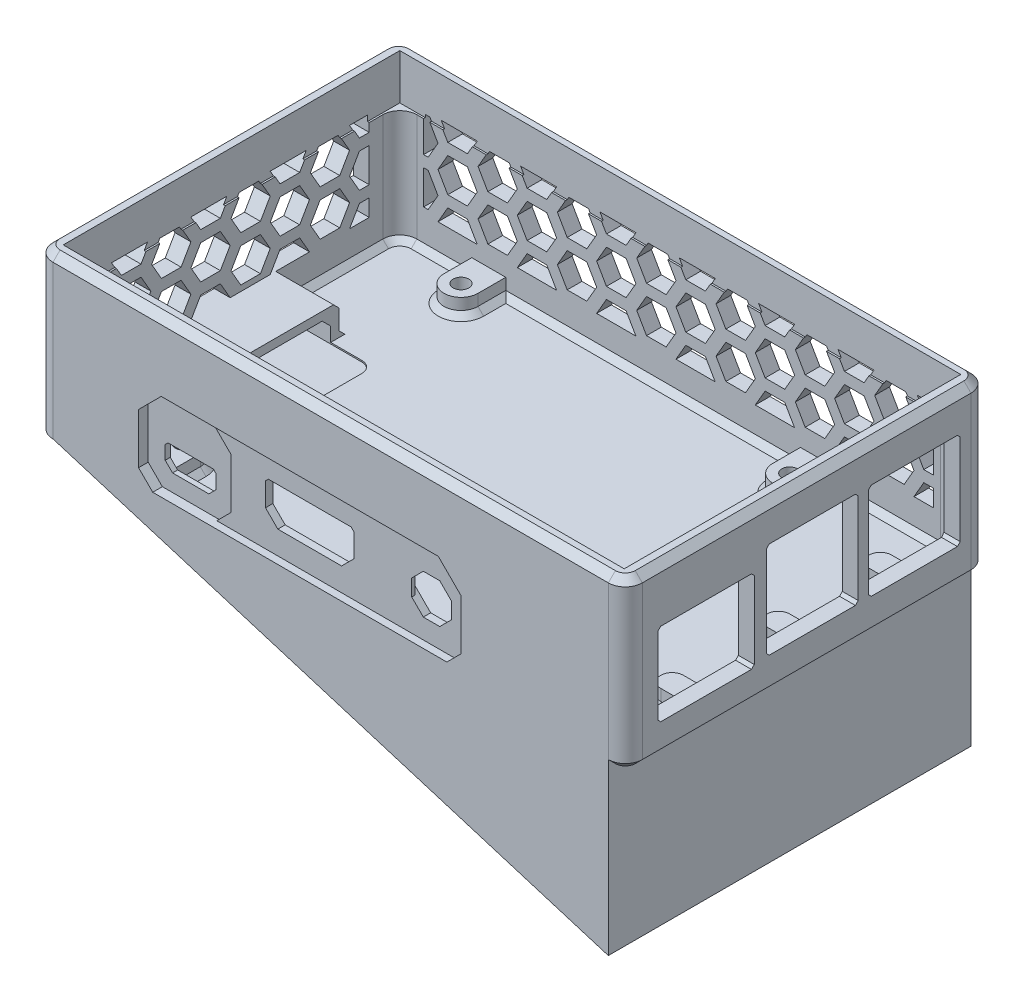
SolidWorks part; units mm, degrees
ref_plane "Front Plane" through (0, 0, 0) normal (0, 0, 1) x (1, 0, 0)
ref_plane "Top Plane" through (0, 0, 0) normal (0, 1, 0) x (1, 0, 0)
ref_plane "Right Plane" through (0, 0, 0) normal (1, 0, 0) x (0, 0, -1)
sketch "Sketch1" plane through (0, 0, 0) normal (0, 1, 0) x (1, 0, 0)
  line L0 (1, 28) -> (0, 28) construction
  line L1 (0, 0) -> (-85, 0) construction
  line L2 (0, 0) -> (0, 56) construction
  line L3 (0, 56) -> (-85, 56) construction
  line L4 (-85, 0) -> (-85, 56) construction
  line L5 (-97, 57.2) -> (1, 57.2) construction
  line L6 (-97, 57.2) -> (-97, -1.2) construction
  line L7 (-97, -1.2) -> (1, -1.2) construction
  line L8 (1, 57.2) -> (1, -1.2) construction
  circle A0 centre (-81.5, 52.5) radius 1.375 construction
  circle A1 centre (-23.5, 52.5) radius 1.375 construction
  circle A2 centre (-81.5, 3.5) radius 1.375 construction
  circle A3 centre (-23.5, 3.5) radius 1.375 construction
  dimension "D3" = 2.75
  dimension "D1" = 56
  dimension "D2" = 85
  dimension "D4" = 49
  dimension "D5" = 58
  dimension "D6" = 3.5
  dimension "D7" = 3.5
  dimension "D8" = 98
  dimension "D9" = 58.4
  dimension "D10" = 15.5
sketch "Sketch2" plane through (0, 0, 0) normal (0, 1, 0) x (1, 0, 0)
  line L0 (-84.5, -2.5) -> (-84.5, 3.5)
  line L2 (-78.5, 3.5) -> (-78.5, -2.5)
  line L3 (-81.5, 3.5) -> (-23.5, 3.5) construction
  line L4 (-81.5, 3.5) -> (-81.5, 52.5) construction
  line L5 (-52.5, 3.5) -> (-52.5, 28) construction
  line L6 (-52.5, 28) -> (-81.5, 28) construction
  line L7 (-84.5, -2.5) -> (-78.5, -2.5)
  line L8 (-20.5, -2.5) -> (-26.5, -2.5)
  line L9 (-26.5, 3.5) -> (-26.5, -2.5)
  line L10 (-20.5, -2.5) -> (-20.5, 3.5)
  line L11 (-20.5, 58.5) -> (-20.5, 52.5)
  line L12 (-26.5, 52.5) -> (-26.5, 58.5)
  line L13 (-20.5, 58.5) -> (-26.5, 58.5)
  line L14 (-84.5, 58.5) -> (-78.5, 58.5)
  line L15 (-78.5, 52.5) -> (-78.5, 58.5)
  line L16 (-84.5, 58.5) -> (-84.5, 52.5)
  arc A0 (-84.5, 3.5) -> (-78.5, 3.5) centre (-81.5, 3.5) cw
  circle A1 centre (-81.5, 3.5) radius 1.375 construction
  circle A2 centre (-81.5, 3.5) radius 1.375
  circle A3 centre (-23.5, 3.5) radius 1.375
  arc A4 (-20.5, 3.5) -> (-26.5, 3.5) centre (-23.5, 3.5) ccw
  arc A5 (-20.5, 52.5) -> (-26.5, 52.5) centre (-23.5, 52.5) cw
  circle A6 centre (-23.5, 52.5) radius 1.375
  circle A7 centre (-81.5, 52.5) radius 1.375
  arc A8 (-84.5, 52.5) -> (-78.5, 52.5) centre (-81.5, 52.5) ccw
  dimension "D1" = 2.75
  dimension "D2" = 6
  dimension "D3" = 6
extrude "Boss-Extrude1" add sketch "Sketch2" along normal blind 4.5
sketch "Sketch4" plane through (0, 0, 0) normal (0, 1, 0) x (1, 0, 0)
  line L0 (0, 28) -> (4, 28) construction
  line L1 (-100, 60) -> (4, 60)
  line L2 (-100, 60) -> (-100, -4)
  line L3 (-100, -4) -> (4, -4)
  line L4 (4, 60) -> (4, -4)
  line L5 (0, 0) -> (0, 56) construction
  line L7 (1, 57.2) -> (1, -1.2) construction
  line L9 (-97, 57.2) -> (-97, -1.2) construction
  dimension "D1" = 64
  dimension "D2" = 3
  dimension "D3" = 3
extrude "Boss-Extrude2" add sketch "Sketch4" along normal blind 1.5
sketch "Sketch5" plane through (0, 0, 0) normal (0, -1, 0) x (1, 0, 0)
  circle A0 centre (-81.5, -3.5) radius 2.6
  circle A1 centre (-23.5, -3.5) radius 2.6
  circle A2 centre (-23.5, -52.5) radius 2.6
  circle A3 centre (-81.5, -52.5) radius 2.6
  dimension "D1" = 5.2
extrude "Cut-Extrude1" cut sketch "Sketch5" against normal offset from surface (2.5 mm away) 2 up to face at (-81.5, 4.5, -1.25)
sketch "Sketch6" plane through (0, 1.5, 0) normal (0, 1, 0) x (1, 0, 0)
  line L0 (-97, 57.2) -> (-97, -1.2) construction
  line L1 (-100, 60) -> (4, 60)
  line L2 (-100, 60) -> (-100, -4)
  line L3 (-100, -4) -> (4, -4)
  line L4 (4, 60) -> (4, -4)
  line L5 (-97.5, 57.7) -> (1.5, 57.7)
  line L6 (-97.5, 57.7) -> (-97.5, -1.7)
  line L7 (-97.5, -1.7) -> (1.5, -1.7)
  line L8 (1.5, 57.7) -> (1.5, -1.7)
  line L9 (-97, 57.2) -> (1, 57.2) construction
  line L10 (1, 57.2) -> (1, -1.2) construction
  line L11 (-97, -1.2) -> (1, -1.2) construction
  dimension "D1" = 0.5
  dimension "D2" = 0.5
  dimension "D3" = 0.5
  dimension "D4" = 0.5
extrude "Boss-Extrude3" add sketch "Sketch6" along normal blind 28
sketch "Sketch10" plane through (0, 1.5, 0) normal (0, 1, 0) x (1, 0, 0)
  line L0 (1.5, 49) -> (-2, 49)
  line L1 (1.5, -1.7) -> (1.5, 57.7) construction
  line L2 (-2, 45) -> (1.5, 45)
  line L3 (1.5, 45) -> (1.5, 49)
  line L4 (1.5, 31) -> (-2, 31)
  line L5 (-2, 27) -> (1.5, 27)
  line L6 (1.5, 27) -> (1.5, 31)
  line L7 (1.5, 12.25) -> (-2, 12.25)
  line L8 (-2, 8.25) -> (1.5, 8.25)
  line L9 (1.5, 8.25) -> (1.5, 12.25)
  line L10 (0, 0) -> (0, 56) construction
  arc A0 (-2, 49) -> (-2, 45) centre (-2, 47) ccw
  arc A1 (-2, 31) -> (-2, 27) centre (-2, 29) ccw
  arc A2 (-2, 12.25) -> (-2, 8.25) centre (-2, 10.25) ccw
  point P19 (-4, 47)
  dimension "D1" = 4
  dimension "D2" = 4
  dimension "D3" = 10.25
  dimension "D4" = 29
  dimension "D5" = 47
extrude "Boss-Extrude4" add sketch "Sketch10" along normal up to surface (3 mm away) up to face at (-23.5, 4.5, -54.35)
sketch "Sketch18" plane through (0, 1.5, 0) normal (0, 1, 0) x (1, 0, 0)
  line L0 (-97.2, 57.4) -> (1.2, 57.4)
  line L1 (-97.5, 57.7) -> (1.5, 57.7)
  line L2 (-97.5, 57.7) -> (-97.5, -1.7)
  line L3 (-97.5, -1.7) -> (1.5, -1.7)
  line L4 (1.5, 57.7) -> (1.5, -1.7)
  line L5 (1.2, 57.4) -> (1.2, -1.4)
  line L6 (-97.2, -1.4) -> (1.2, -1.4)
  line L7 (-97.2, 57.4) -> (-97.2, -1.4)
  dimension "D1" = 0.3
extrude "Boss-Extrude6" add sketch "Sketch18" along normal blind 20
sketch "Sketch19" plane through (0, 0, -60) normal (0, 0, -1) x (-1, 0, 0)
  line L4 (5.5981, 8.5) -> (7.3301, 9.5) construction
  line L5 (6.4641, 7) -> (4.7321, 10)
  line L6 (4.7321, 10) -> (1.2679, 10)
  line L7 (1.2679, 10) -> (-0.4641, 7)
  line L8 (3, 7) -> (93, 7)
  line L9 (93, 7) -> (93, 22.5)
  line L10 (93, 22.5) -> (3, 22.5)
  line L11 (3, 22.5) -> (3, 7)
  line L12 (3, 7) -> (93, 7)
  line L13 (93, 7) -> (93, 22.5)
  line L14 (93, 22.5) -> (3, 22.5)
  line L15 (3, 22.5) -> (3, 7)
  line L16 (-0.4641, 7) -> (1.2679, 4)
  line L17 (1.2679, 4) -> (4.7321, 4)
  line L18 (4.7321, 4) -> (6.4641, 7)
  line L19 (11.6603, 14) -> (8.1962, 14)
  line L20 (8.1962, 14) -> (6.4641, 11)
  line L21 (6.4641, 11) -> (8.1962, 8)
  line L22 (8.1962, 8) -> (11.6603, 8)
  line L23 (11.6603, 8) -> (13.3923, 11)
  line L24 (13.3923, 11) -> (11.6603, 14)
  line L25 (20.4641, 7) -> (18.7321, 10)
  line L26 (18.7321, 10) -> (15.2679, 10)
  line L27 (15.2679, 10) -> (13.5359, 7)
  line L28 (13.5359, 7) -> (15.2679, 4)
  line L29 (15.2679, 4) -> (18.7321, 4)
  line L30 (18.7321, 4) -> (20.4641, 7)
  line L31 (25.6603, 14) -> (22.1962, 14)
  line L32 (22.1962, 14) -> (20.4641, 11)
  line L33 (20.4641, 11) -> (22.1962, 8)
  line L34 (22.1962, 8) -> (25.6603, 8)
  line L35 (25.6603, 8) -> (27.3923, 11)
  line L36 (27.3923, 11) -> (25.6603, 14)
  line L37 (19.5981, 8.5) -> (21.3301, 9.5) construction
  line L38 (34.4641, 7) -> (32.7321, 10)
  line L39 (32.7321, 10) -> (29.2679, 10)
  line L40 (29.2679, 10) -> (27.5359, 7)
  line L41 (27.5359, 7) -> (29.2679, 4)
  line L42 (29.2679, 4) -> (32.7321, 4)
  line L43 (32.7321, 4) -> (34.4641, 7)
  line L44 (39.6603, 14) -> (36.1962, 14)
  line L45 (36.1962, 14) -> (34.4641, 11)
  line L46 (34.4641, 11) -> (36.1962, 8)
  line L47 (36.1962, 8) -> (39.6603, 8)
  line L48 (39.6603, 8) -> (41.3923, 11)
  line L49 (41.3923, 11) -> (39.6603, 14)
  line L50 (33.5981, 8.5) -> (35.3301, 9.5) construction
  line L51 (48.4641, 7) -> (46.7321, 10)
  line L52 (46.7321, 10) -> (43.2679, 10)
  line L53 (43.2679, 10) -> (41.5359, 7)
  line L54 (41.5359, 7) -> (43.2679, 4)
  line L55 (43.2679, 4) -> (46.7321, 4)
  line L56 (46.7321, 4) -> (48.4641, 7)
  line L57 (53.6603, 14) -> (50.1962, 14)
  line L58 (50.1962, 14) -> (48.4641, 11)
  line L59 (48.4641, 11) -> (50.1962, 8)
  line L60 (50.1962, 8) -> (53.6603, 8)
  line L61 (53.6603, 8) -> (55.3923, 11)
  line L62 (55.3923, 11) -> (53.6603, 14)
  line L63 (47.5981, 8.5) -> (49.3301, 9.5) construction
  line L64 (62.4641, 7) -> (60.7321, 10)
  line L65 (60.7321, 10) -> (57.2679, 10)
  line L66 (57.2679, 10) -> (55.5359, 7)
  line L67 (55.5359, 7) -> (57.2679, 4)
  line L68 (57.2679, 4) -> (60.7321, 4)
  line L69 (60.7321, 4) -> (62.4641, 7)
  line L70 (67.6603, 14) -> (64.1962, 14)
  line L71 (64.1962, 14) -> (62.4641, 11)
  line L72 (62.4641, 11) -> (64.1962, 8)
  line L73 (64.1962, 8) -> (67.6603, 8)
  line L74 (67.6603, 8) -> (69.3923, 11)
  line L75 (69.3923, 11) -> (67.6603, 14)
  line L76 (61.5981, 8.5) -> (63.3301, 9.5) construction
  line L77 (76.4641, 7) -> (74.7321, 10)
  line L78 (74.7321, 10) -> (71.2679, 10)
  line L79 (71.2679, 10) -> (69.5359, 7)
  line L80 (69.5359, 7) -> (71.2679, 4)
  line L81 (71.2679, 4) -> (74.7321, 4)
  line L82 (74.7321, 4) -> (76.4641, 7)
  line L83 (81.6603, 14) -> (78.1962, 14)
  line L84 (78.1962, 14) -> (76.4641, 11)
  line L85 (76.4641, 11) -> (78.1962, 8)
  line L86 (78.1962, 8) -> (81.6603, 8)
  line L87 (81.6603, 8) -> (83.3923, 11)
  line L88 (83.3923, 11) -> (81.6603, 14)
  line L89 (75.5981, 8.5) -> (77.3301, 9.5) construction
  line L90 (90.4641, 7) -> (88.7321, 10)
  line L91 (88.7321, 10) -> (85.2679, 10)
  line L92 (85.2679, 10) -> (83.5359, 7)
  line L93 (83.5359, 7) -> (85.2679, 4)
  line L94 (85.2679, 4) -> (88.7321, 4)
  line L95 (88.7321, 4) -> (90.4641, 7)
  line L96 (95.6603, 14) -> (92.1962, 14)
  line L97 (92.1962, 14) -> (90.4641, 11)
  line L98 (90.4641, 11) -> (92.1962, 8)
  line L99 (92.1962, 8) -> (95.6603, 8)
  line L100 (95.6603, 8) -> (97.3923, 11)
  line L101 (97.3923, 11) -> (95.6603, 14)
  line L102 (89.5981, 8.5) -> (91.3301, 9.5) construction
  line L103 (20.4641, 15) -> (18.7321, 18)
  line L104 (18.7321, 18) -> (15.2679, 18)
  line L105 (15.2679, 18) -> (13.5359, 15)
  line L106 (13.5359, 15) -> (15.2679, 12)
  line L107 (15.2679, 12) -> (18.7321, 12)
  line L108 (18.7321, 12) -> (20.4641, 15)
  line L109 (25.6603, 22) -> (22.1962, 22)
  line L110 (22.1962, 22) -> (20.4641, 19)
  line L111 (20.4641, 19) -> (22.1962, 16)
  line L112 (22.1962, 16) -> (25.6603, 16)
  line L113 (25.6603, 16) -> (27.3923, 19)
  line L114 (27.3923, 19) -> (25.6603, 22)
  line L115 (19.5981, 16.5) -> (21.3301, 17.5) construction
  line L116 (34.4641, 15) -> (32.7321, 18)
  line L117 (32.7321, 18) -> (29.2679, 18)
  line L118 (29.2679, 18) -> (27.5359, 15)
  line L119 (27.5359, 15) -> (29.2679, 12)
  line L120 (29.2679, 12) -> (32.7321, 12)
  line L121 (32.7321, 12) -> (34.4641, 15)
  line L122 (39.6603, 22) -> (36.1962, 22)
  line L123 (36.1962, 22) -> (34.4641, 19)
  line L124 (34.4641, 19) -> (36.1962, 16)
  line L125 (36.1962, 16) -> (39.6603, 16)
  line L126 (39.6603, 16) -> (41.3923, 19)
  line L127 (41.3923, 19) -> (39.6603, 22)
  line L128 (33.5981, 16.5) -> (35.3301, 17.5) construction
  line L129 (48.4641, 15) -> (46.7321, 18)
  line L130 (46.7321, 18) -> (43.2679, 18)
  line L131 (43.2679, 18) -> (41.5359, 15)
  line L132 (41.5359, 15) -> (43.2679, 12)
  line L133 (43.2679, 12) -> (46.7321, 12)
  line L134 (46.7321, 12) -> (48.4641, 15)
  line L135 (53.6603, 22) -> (50.1962, 22)
  line L136 (50.1962, 22) -> (48.4641, 19)
  line L137 (48.4641, 19) -> (50.1962, 16)
  line L138 (50.1962, 16) -> (53.6603, 16)
  line L139 (53.6603, 16) -> (55.3923, 19)
  line L140 (55.3923, 19) -> (53.6603, 22)
  line L141 (47.5981, 16.5) -> (49.3301, 17.5) construction
  line L142 (62.4641, 15) -> (60.7321, 18)
  line L143 (60.7321, 18) -> (57.2679, 18)
  line L144 (57.2679, 18) -> (55.5359, 15)
  line L145 (55.5359, 15) -> (57.2679, 12)
  line L146 (57.2679, 12) -> (60.7321, 12)
  line L147 (60.7321, 12) -> (62.4641, 15)
  line L148 (67.6603, 22) -> (64.1962, 22)
  line L149 (64.1962, 22) -> (62.4641, 19)
  line L150 (62.4641, 19) -> (64.1962, 16)
  line L151 (64.1962, 16) -> (67.6603, 16)
  line L152 (67.6603, 16) -> (69.3923, 19)
  line L153 (69.3923, 19) -> (67.6603, 22)
  line L154 (61.5981, 16.5) -> (63.3301, 17.5) construction
  line L155 (76.4641, 15) -> (74.7321, 18)
  line L156 (74.7321, 18) -> (71.2679, 18)
  line L157 (71.2679, 18) -> (69.5359, 15)
  line L158 (69.5359, 15) -> (71.2679, 12)
  line L159 (71.2679, 12) -> (74.7321, 12)
  line L160 (74.7321, 12) -> (76.4641, 15)
  line L161 (81.6603, 22) -> (78.1962, 22)
  line L162 (78.1962, 22) -> (76.4641, 19)
  line L163 (76.4641, 19) -> (78.1962, 16)
  line L164 (78.1962, 16) -> (81.6603, 16)
  line L165 (81.6603, 16) -> (83.3923, 19)
  line L166 (83.3923, 19) -> (81.6603, 22)
  line L167 (75.5981, 16.5) -> (77.3301, 17.5) construction
  line L168 (90.4641, 15) -> (88.7321, 18)
  line L169 (88.7321, 18) -> (85.2679, 18)
  line L170 (85.2679, 18) -> (83.5359, 15)
  line L171 (83.5359, 15) -> (85.2679, 12)
  line L172 (85.2679, 12) -> (88.7321, 12)
  line L173 (88.7321, 12) -> (90.4641, 15)
  line L174 (95.6603, 22) -> (92.1962, 22)
  line L175 (92.1962, 22) -> (90.4641, 19)
  line L176 (90.4641, 19) -> (92.1962, 16)
  line L177 (92.1962, 16) -> (95.6603, 16)
  line L178 (95.6603, 16) -> (97.3923, 19)
  line L179 (97.3923, 19) -> (95.6603, 22)
  line L180 (89.5981, 16.5) -> (91.3301, 17.5) construction
  line L181 (20.4641, 23) -> (18.7321, 26)
  line L182 (18.7321, 26) -> (15.2679, 26)
  line L183 (15.2679, 26) -> (13.5359, 23)
  line L184 (13.5359, 23) -> (15.2679, 20)
  line L185 (15.2679, 20) -> (18.7321, 20)
  line L186 (18.7321, 20) -> (20.4641, 23)
  line L187 (25.6603, 30) -> (22.1962, 30)
  line L188 (22.1962, 30) -> (20.4641, 27)
  line L189 (20.4641, 27) -> (22.1962, 24)
  line L190 (22.1962, 24) -> (25.6603, 24)
  line L191 (25.6603, 24) -> (27.3923, 27)
  line L192 (27.3923, 27) -> (25.6603, 30)
  line L193 (19.5981, 24.5) -> (21.3301, 25.5) construction
  line L194 (34.4641, 23) -> (32.7321, 26)
  line L195 (32.7321, 26) -> (29.2679, 26)
  line L196 (29.2679, 26) -> (27.5359, 23)
  line L197 (27.5359, 23) -> (29.2679, 20)
  line L198 (29.2679, 20) -> (32.7321, 20)
  line L199 (32.7321, 20) -> (34.4641, 23)
  line L200 (39.6603, 30) -> (36.1962, 30)
  line L201 (36.1962, 30) -> (34.4641, 27)
  line L202 (34.4641, 27) -> (36.1962, 24)
  line L203 (36.1962, 24) -> (39.6603, 24)
  line L204 (39.6603, 24) -> (41.3923, 27)
  line L205 (41.3923, 27) -> (39.6603, 30)
  line L206 (33.5981, 24.5) -> (35.3301, 25.5) construction
  line L207 (48.4641, 23) -> (46.7321, 26)
  line L208 (46.7321, 26) -> (43.2679, 26)
  line L209 (43.2679, 26) -> (41.5359, 23)
  line L210 (41.5359, 23) -> (43.2679, 20)
  line L211 (43.2679, 20) -> (46.7321, 20)
  line L212 (46.7321, 20) -> (48.4641, 23)
  line L213 (53.6603, 30) -> (50.1962, 30)
  line L214 (50.1962, 30) -> (48.4641, 27)
  line L215 (48.4641, 27) -> (50.1962, 24)
  line L216 (50.1962, 24) -> (53.6603, 24)
  line L217 (53.6603, 24) -> (55.3923, 27)
  line L218 (55.3923, 27) -> (53.6603, 30)
  line L219 (47.5981, 24.5) -> (49.3301, 25.5) construction
  line L220 (62.4641, 23) -> (60.7321, 26)
  line L221 (60.7321, 26) -> (57.2679, 26)
  line L222 (57.2679, 26) -> (55.5359, 23)
  line L223 (55.5359, 23) -> (57.2679, 20)
  line L224 (57.2679, 20) -> (60.7321, 20)
  line L225 (60.7321, 20) -> (62.4641, 23)
  line L226 (67.6603, 30) -> (64.1962, 30)
  line L227 (64.1962, 30) -> (62.4641, 27)
  line L228 (62.4641, 27) -> (64.1962, 24)
  line L229 (64.1962, 24) -> (67.6603, 24)
  line L230 (67.6603, 24) -> (69.3923, 27)
  line L231 (69.3923, 27) -> (67.6603, 30)
  line L232 (61.5981, 24.5) -> (63.3301, 25.5) construction
  line L233 (76.4641, 23) -> (74.7321, 26)
  line L234 (74.7321, 26) -> (71.2679, 26)
  line L235 (71.2679, 26) -> (69.5359, 23)
  line L236 (69.5359, 23) -> (71.2679, 20)
  line L237 (71.2679, 20) -> (74.7321, 20)
  line L238 (74.7321, 20) -> (76.4641, 23)
  line L239 (81.6603, 30) -> (78.1962, 30)
  line L240 (78.1962, 30) -> (76.4641, 27)
  line L241 (76.4641, 27) -> (78.1962, 24)
  line L242 (78.1962, 24) -> (81.6603, 24)
  line L243 (81.6603, 24) -> (83.3923, 27)
  line L244 (83.3923, 27) -> (81.6603, 30)
  line L245 (75.5981, 24.5) -> (77.3301, 25.5) construction
  line L246 (90.4641, 23) -> (88.7321, 26)
  line L247 (88.7321, 26) -> (85.2679, 26)
  line L248 (85.2679, 26) -> (83.5359, 23)
  line L249 (83.5359, 23) -> (85.2679, 20)
  line L250 (85.2679, 20) -> (88.7321, 20)
  line L251 (88.7321, 20) -> (90.4641, 23)
  line L252 (95.6603, 30) -> (92.1962, 30)
  line L253 (92.1962, 30) -> (90.4641, 27)
  line L254 (90.4641, 27) -> (92.1962, 24)
  line L255 (92.1962, 24) -> (95.6603, 24)
  line L256 (95.6603, 24) -> (97.3923, 27)
  line L257 (97.3923, 27) -> (95.6603, 30)
  line L258 (89.5981, 24.5) -> (91.3301, 25.5) construction
  line L259 (6.4641, 15) -> (4.7321, 18)
  line L260 (4.7321, 18) -> (1.2679, 18)
  line L261 (1.2679, 18) -> (-0.4641, 15)
  line L262 (-0.4641, 15) -> (1.2679, 12)
  line L263 (1.2679, 12) -> (4.7321, 12)
  line L264 (4.7321, 12) -> (6.4641, 15)
  line L265 (11.6603, 22) -> (8.1962, 22)
  line L266 (8.1962, 22) -> (6.4641, 19)
  line L267 (6.4641, 19) -> (8.1962, 16)
  line L268 (8.1962, 16) -> (11.6603, 16)
  line L269 (11.6603, 16) -> (13.3923, 19)
  line L270 (13.3923, 19) -> (11.6603, 22)
  line L271 (5.5981, 16.5) -> (7.3301, 17.5) construction
  line L272 (6.4641, 23) -> (4.7321, 26)
  line L273 (4.7321, 26) -> (1.2679, 26)
  line L274 (1.2679, 26) -> (-0.4641, 23)
  line L275 (-0.4641, 23) -> (1.2679, 20)
  line L276 (1.2679, 20) -> (4.7321, 20)
  line L277 (4.7321, 20) -> (6.4641, 23)
  line L278 (11.6603, 30) -> (8.1962, 30)
  line L279 (8.1962, 30) -> (6.4641, 27)
  line L280 (6.4641, 27) -> (8.1962, 24)
  line L281 (8.1962, 24) -> (11.6603, 24)
  line L282 (11.6603, 24) -> (13.3923, 27)
  line L283 (13.3923, 27) -> (11.6603, 30)
  line L284 (5.5981, 24.5) -> (7.3301, 25.5) construction
  circle A0 centre (3, 7) radius 3 construction
  circle A1 centre (9.9282, 11) radius 3 construction
  circle A2 centre (17, 7) radius 3 construction
  circle A3 centre (23.9282, 11) radius 3 construction
  circle A4 centre (31, 7) radius 3 construction
  circle A5 centre (37.9282, 11) radius 3 construction
  circle A6 centre (45, 7) radius 3 construction
  circle A7 centre (51.9282, 11) radius 3 construction
  circle A8 centre (59, 7) radius 3 construction
  circle A9 centre (65.9282, 11) radius 3 construction
  circle A10 centre (73, 7) radius 3 construction
  circle A11 centre (79.9282, 11) radius 3 construction
  circle A12 centre (87, 7) radius 3 construction
  circle A13 centre (93.9282, 11) radius 3 construction
  circle A14 centre (17, 15) radius 3 construction
  circle A15 centre (23.9282, 19) radius 3 construction
  circle A16 centre (31, 15) radius 3 construction
  circle A17 centre (37.9282, 19) radius 3 construction
  circle A18 centre (45, 15) radius 3 construction
  circle A19 centre (51.9282, 19) radius 3 construction
  circle A20 centre (59, 15) radius 3 construction
  circle A21 centre (65.9282, 19) radius 3 construction
  circle A22 centre (73, 15) radius 3 construction
  circle A23 centre (79.9282, 19) radius 3 construction
  circle A24 centre (87, 15) radius 3 construction
  circle A25 centre (93.9282, 19) radius 3 construction
  circle A26 centre (17, 23) radius 3 construction
  circle A27 centre (23.9282, 27) radius 3 construction
  circle A28 centre (31, 23) radius 3 construction
  circle A29 centre (37.9282, 27) radius 3 construction
  circle A30 centre (45, 23) radius 3 construction
  circle A31 centre (51.9282, 27) radius 3 construction
  circle A32 centre (59, 23) radius 3 construction
  circle A33 centre (65.9282, 27) radius 3 construction
  circle A34 centre (73, 23) radius 3 construction
  circle A35 centre (79.9282, 27) radius 3 construction
  circle A36 centre (87, 23) radius 3 construction
  circle A37 centre (93.9282, 27) radius 3 construction
  circle A38 centre (3, 15) radius 3 construction
  circle A39 centre (9.9282, 19) radius 3 construction
  circle A40 centre (3, 23) radius 3 construction
  circle A41 centre (9.9282, 27) radius 3 construction
  dimension "D2" = 6
  dimension "D3" = 2
  dimension "D1" = 7
  dimension "D4" = 7
  dimension "D5" = 3
extrude "Cut-Extrude8" cut sketch "Sketch19" against normal up to next (2.6 mm away) contours L6 L15 L12 L5 | L263 L264 L259 L260 L15 | L276 L277 L14 L15 | L185 L186 L14 L184 | L269 L270 L265 L266 L267 L268 | L23 L24 L19 L20 L21 L22 | L107 L108 L103 L104 L105 L106 | L26 L27 L12 L25 | L35 L36 L31 L32 L33 L34 | L39 L40 L12 L38 | L48 L49 L44 L45 L46 L47 | L52 L53 L12 L51 | L61 L62 L57 L58 L59 L60 | L65 L66 L12 L64 | L74 L75 L70 L71 L72 L73 | L78 L79 L12 L77 | L87 L88 L83 L84 L85 L86 | L91 L92 L12 L90 | L98 L99 L13 L96 L97 | L176 L177 L13 L174 L175 | L250 L251 L14 L249 | L172 L173 L168 L169 L170 L171 | L165 L166 L161 L162 L163 L164 | L237 L238 L14 L236 | L159 L160 L155 L156 L157 L158 | L152 L153 L148 L149 L150 L151 | L224 L225 L14 L223 | L146 L147 L142 L143 L144 L145 | L139 L140 L135 L136 L137 L138 | L211 L212 L14 L210 | L198 L199 L14 L197 | L113 L114 L109 L110 L111 L112 | L120 L121 L116 L117 L118 L119 | L126 L127 L122 L123 L124 L125 | L133 L134 L129 L130 L131 L132 region at (-4.3472, 8.3333, -60) region at (-17, 8.3333, -60) region at (-4.3472, 15, -60) region at (-31, 8.3333, -60) region at (-4.2622, 21.3725, -60) region at (-45, 8.3333, -60) region at (-59, 8.3333, -60) region at (-17, 21.3725, -60) region at (-73, 8.3333, -60) region at (-31, 21.3725, -60) region at (-87, 8.3333, -60) region at (-45, 21.3725, -60) region at (-59, 21.3725, -60) region at (-92.0902, 11, -60) region at (-73, 21.3725, -60) region at (-92.0902, 19, -60) region at (-87, 21.3725, -60) region at (-9.9282, 11, -60) region at (-23.9282, 11, -60) region at (-37.9282, 11, -60) region at (-51.9282, 11, -60) region at (-65.9282, 11, -60) region at (-79.9282, 11, -60) region at (-17, 15, -60) region at (-23.9282, 19, -60) region at (-31, 15, -60) region at (-37.9282, 19, -60) region at (-45, 15, -60) region at (-51.9282, 19, -60) region at (-59, 15, -60) region at (-65.9282, 19, -60) region at (-73, 15, -60) region at (-79.9282, 19, -60) region at (-87, 15, -60) region at (-9.9282, 19, -60)
sketch "Sketch21" plane through (-100, 0, 0) normal (-1, 0, 0) x (0, 0, 1)
  line L0 (-60, 29.5) -> (4, 29.5) construction
  line L1 (-52, 22.5) -> (-4, 22.5)
  line L2 (-52, 22.5) -> (-52, 7)
  line L3 (-52, 7) -> (-4, 7)
  line L4 (-4, 22.5) -> (-4, 7)
  line L5 (-60, 0) -> (4, 0) construction
  line L6 (-60, 29.5) -> (-60, 0) construction
  line L7 (4, 29.5) -> (4, 0) construction
  line L8 (-52, 7) -> (-45.0718, 11) construction
  line L9 (-53.7321, 10) -> (-55.4641, 7)
  line L10 (-55.4641, 7) -> (-53.7321, 4)
  line L11 (-53.7321, 4) -> (-50.2679, 4)
  line L12 (-50.2679, 4) -> (-48.5359, 7)
  line L13 (-48.5359, 7) -> (-50.2679, 10)
  line L14 (-50.2679, 10) -> (-53.7321, 10)
  line L15 (-43.3397, 14) -> (-46.8038, 14)
  line L16 (-46.8038, 14) -> (-48.5359, 11)
  line L17 (-48.5359, 11) -> (-46.8038, 8)
  line L18 (-46.8038, 8) -> (-43.3397, 8)
  line L19 (-43.3397, 8) -> (-41.6077, 11)
  line L20 (-41.6077, 11) -> (-43.3397, 14)
  line L21 (-39.7321, 10) -> (-41.4641, 7)
  line L22 (-41.4641, 7) -> (-39.7321, 4)
  line L23 (-39.7321, 4) -> (-36.2679, 4)
  line L24 (-36.2679, 4) -> (-34.5359, 7)
  line L25 (-34.5359, 7) -> (-36.2679, 10)
  line L26 (-36.2679, 10) -> (-39.7321, 10)
  line L27 (-29.3397, 14) -> (-32.8038, 14)
  line L28 (-32.8038, 14) -> (-34.5359, 11)
  line L29 (-34.5359, 11) -> (-32.8038, 8)
  line L30 (-32.8038, 8) -> (-29.3397, 8)
  line L31 (-29.3397, 8) -> (-27.6077, 11)
  line L32 (-27.6077, 11) -> (-29.3397, 14)
  line L33 (-38, 7) -> (-31.0718, 11) construction
  line L34 (-25.7321, 10) -> (-27.4641, 7)
  line L35 (-27.4641, 7) -> (-25.7321, 4)
  line L36 (-25.7321, 4) -> (-22.2679, 4)
  line L37 (-22.2679, 4) -> (-20.5359, 7)
  line L38 (-20.5359, 7) -> (-22.2679, 10)
  line L39 (-22.2679, 10) -> (-25.7321, 10)
  line L40 (-15.3397, 14) -> (-18.8038, 14)
  line L41 (-18.8038, 14) -> (-20.5359, 11)
  line L42 (-20.5359, 11) -> (-18.8038, 8)
  line L43 (-18.8038, 8) -> (-15.3397, 8)
  line L44 (-15.3397, 8) -> (-13.6077, 11)
  line L45 (-13.6077, 11) -> (-15.3397, 14)
  line L46 (-24, 7) -> (-17.0718, 11) construction
  line L47 (-11.7321, 10) -> (-13.4641, 7)
  line L48 (-13.4641, 7) -> (-11.7321, 4)
  line L49 (-11.7321, 4) -> (-8.2679, 4)
  line L50 (-8.2679, 4) -> (-6.5359, 7)
  line L51 (-6.5359, 7) -> (-8.2679, 10)
  line L52 (-8.2679, 10) -> (-11.7321, 10)
  line L53 (-1.3397, 14) -> (-4.8038, 14)
  line L54 (-4.8038, 14) -> (-6.5359, 11)
  line L55 (-6.5359, 11) -> (-4.8038, 8)
  line L56 (-4.8038, 8) -> (-1.3397, 8)
  line L57 (-1.3397, 8) -> (0.3923, 11)
  line L58 (0.3923, 11) -> (-1.3397, 14)
  line L59 (-10, 7) -> (-3.0718, 11) construction
  line L60 (-39.7321, 18) -> (-41.4641, 15)
  line L61 (-41.4641, 15) -> (-39.7321, 12)
  line L62 (-39.7321, 12) -> (-36.2679, 12)
  line L63 (-36.2679, 12) -> (-34.5359, 15)
  line L64 (-34.5359, 15) -> (-36.2679, 18)
  line L65 (-36.2679, 18) -> (-39.7321, 18)
  line L66 (-29.3397, 22) -> (-32.8038, 22)
  line L67 (-32.8038, 22) -> (-34.5359, 19)
  line L68 (-34.5359, 19) -> (-32.8038, 16)
  line L69 (-32.8038, 16) -> (-29.3397, 16)
  line L70 (-29.3397, 16) -> (-27.6077, 19)
  line L71 (-27.6077, 19) -> (-29.3397, 22)
  line L72 (-38, 15) -> (-31.0718, 19) construction
  line L73 (-25.7321, 18) -> (-27.4641, 15)
  line L74 (-27.4641, 15) -> (-25.7321, 12)
  line L75 (-25.7321, 12) -> (-22.2679, 12)
  line L76 (-22.2679, 12) -> (-20.5359, 15)
  line L77 (-20.5359, 15) -> (-22.2679, 18)
  line L78 (-22.2679, 18) -> (-25.7321, 18)
  line L79 (-15.3397, 22) -> (-18.8038, 22)
  line L80 (-18.8038, 22) -> (-20.5359, 19)
  line L81 (-20.5359, 19) -> (-18.8038, 16)
  line L82 (-18.8038, 16) -> (-15.3397, 16)
  line L83 (-15.3397, 16) -> (-13.6077, 19)
  line L84 (-13.6077, 19) -> (-15.3397, 22)
  line L85 (-24, 15) -> (-17.0718, 19) construction
  line L86 (-11.7321, 18) -> (-13.4641, 15)
  line L87 (-13.4641, 15) -> (-11.7321, 12)
  line L88 (-11.7321, 12) -> (-8.2679, 12)
  line L89 (-8.2679, 12) -> (-6.5359, 15)
  line L90 (-6.5359, 15) -> (-8.2679, 18)
  line L91 (-8.2679, 18) -> (-11.7321, 18)
  line L92 (-1.3397, 22) -> (-4.8038, 22)
  line L93 (-4.8038, 22) -> (-6.5359, 19)
  line L94 (-6.5359, 19) -> (-4.8038, 16)
  line L95 (-4.8038, 16) -> (-1.3397, 16)
  line L96 (-1.3397, 16) -> (0.3923, 19)
  line L97 (0.3923, 19) -> (-1.3397, 22)
  line L98 (-10, 15) -> (-3.0718, 19) construction
  line L99 (-39.7321, 26) -> (-41.4641, 23)
  line L100 (-41.4641, 23) -> (-39.7321, 20)
  line L101 (-39.7321, 20) -> (-36.2679, 20)
  line L102 (-36.2679, 20) -> (-34.5359, 23)
  line L103 (-34.5359, 23) -> (-36.2679, 26)
  line L104 (-36.2679, 26) -> (-39.7321, 26)
  line L105 (-29.3397, 30) -> (-32.8038, 30)
  line L106 (-32.8038, 30) -> (-34.5359, 27)
  line L107 (-34.5359, 27) -> (-32.8038, 24)
  line L108 (-32.8038, 24) -> (-29.3397, 24)
  line L109 (-29.3397, 24) -> (-27.6077, 27)
  line L110 (-27.6077, 27) -> (-29.3397, 30)
  line L111 (-38, 23) -> (-31.0718, 27) construction
  line L112 (-25.7321, 26) -> (-27.4641, 23)
  line L113 (-27.4641, 23) -> (-25.7321, 20)
  line L114 (-25.7321, 20) -> (-22.2679, 20)
  line L115 (-22.2679, 20) -> (-20.5359, 23)
  line L116 (-20.5359, 23) -> (-22.2679, 26)
  line L117 (-22.2679, 26) -> (-25.7321, 26)
  line L118 (-15.3397, 30) -> (-18.8038, 30)
  line L119 (-18.8038, 30) -> (-20.5359, 27)
  line L120 (-20.5359, 27) -> (-18.8038, 24)
  line L121 (-18.8038, 24) -> (-15.3397, 24)
  line L122 (-15.3397, 24) -> (-13.6077, 27)
  line L123 (-13.6077, 27) -> (-15.3397, 30)
  line L124 (-24, 23) -> (-17.0718, 27) construction
  line L125 (-11.7321, 26) -> (-13.4641, 23)
  line L126 (-13.4641, 23) -> (-11.7321, 20)
  line L127 (-11.7321, 20) -> (-8.2679, 20)
  line L128 (-8.2679, 20) -> (-6.5359, 23)
  line L129 (-6.5359, 23) -> (-8.2679, 26)
  line L130 (-8.2679, 26) -> (-11.7321, 26)
  line L131 (-1.3397, 30) -> (-4.8038, 30)
  line L132 (-4.8038, 30) -> (-6.5359, 27)
  line L133 (-6.5359, 27) -> (-4.8038, 24)
  line L134 (-4.8038, 24) -> (-1.3397, 24)
  line L135 (-1.3397, 24) -> (0.3923, 27)
  line L136 (0.3923, 27) -> (-1.3397, 30)
  line L137 (-10, 23) -> (-3.0718, 27) construction
  line L138 (-53.7321, 18) -> (-55.4641, 15)
  line L139 (-55.4641, 15) -> (-53.7321, 12)
  line L140 (-53.7321, 12) -> (-50.2679, 12)
  line L141 (-50.2679, 12) -> (-48.5359, 15)
  line L142 (-48.5359, 15) -> (-50.2679, 18)
  line L143 (-50.2679, 18) -> (-53.7321, 18)
  line L144 (-43.3397, 22) -> (-46.8038, 22)
  line L145 (-46.8038, 22) -> (-48.5359, 19)
  line L146 (-48.5359, 19) -> (-46.8038, 16)
  line L147 (-46.8038, 16) -> (-43.3397, 16)
  line L148 (-43.3397, 16) -> (-41.6077, 19)
  line L149 (-41.6077, 19) -> (-43.3397, 22)
  line L150 (-52, 15) -> (-45.0718, 19) construction
  line L151 (-53.7321, 26) -> (-55.4641, 23)
  line L152 (-55.4641, 23) -> (-53.7321, 20)
  line L153 (-53.7321, 20) -> (-50.2679, 20)
  line L154 (-50.2679, 20) -> (-48.5359, 23)
  line L155 (-48.5359, 23) -> (-50.2679, 26)
  line L156 (-50.2679, 26) -> (-53.7321, 26)
  line L157 (-43.3397, 30) -> (-46.8038, 30)
  line L158 (-46.8038, 30) -> (-48.5359, 27)
  line L159 (-48.5359, 27) -> (-46.8038, 24)
  line L160 (-46.8038, 24) -> (-43.3397, 24)
  line L161 (-43.3397, 24) -> (-41.6077, 27)
  line L162 (-41.6077, 27) -> (-43.3397, 30)
  line L163 (-52, 23) -> (-45.0718, 27) construction
  circle A0 centre (-52, 7) radius 3 construction
  circle A1 centre (-45.0718, 11) radius 3 construction
  circle A2 centre (-38, 7) radius 3 construction
  circle A3 centre (-31.0718, 11) radius 3 construction
  circle A4 centre (-24, 7) radius 3 construction
  circle A5 centre (-17.0718, 11) radius 3 construction
  circle A6 centre (-10, 7) radius 3 construction
  circle A7 centre (-3.0718, 11) radius 3 construction
  circle A8 centre (-38, 15) radius 3 construction
  circle A9 centre (-31.0718, 19) radius 3 construction
  circle A10 centre (-24, 15) radius 3 construction
  circle A11 centre (-17.0718, 19) radius 3 construction
  circle A12 centre (-10, 15) radius 3 construction
  circle A13 centre (-3.0718, 19) radius 3 construction
  circle A14 centre (-38, 23) radius 3 construction
  circle A15 centre (-31.0718, 27) radius 3 construction
  circle A16 centre (-24, 23) radius 3 construction
  circle A17 centre (-17.0718, 27) radius 3 construction
  circle A18 centre (-10, 23) radius 3 construction
  circle A19 centre (-3.0718, 27) radius 3 construction
  circle A20 centre (-52, 15) radius 3 construction
  circle A21 centre (-45.0718, 19) radius 3 construction
  circle A22 centre (-52, 23) radius 3 construction
  circle A23 centre (-45.0718, 27) radius 3 construction
  point P8 (-52, 14.75)
  dimension "D1" = 7
  dimension "D2" = 7
  dimension "D3" = 8
  dimension "D4" = 8
  dimension "D5" = 2
  dimension "D6" = 6
  dimension "D7" = 4
  dimension "D8" = 3
extrude "Cut-Extrude9" cut sketch "Sketch21" against normal blind 10 contours L13 L14 L2 L3 | L142 L143 L2 L140 L141 | L153 L154 L1 L2 | L148 L149 L144 L145 L146 L147 | L101 L102 L1 L100 | L70 L71 L66 L67 L68 L69 | L114 L115 L1 L113 | L127 L128 L1 L126 | L94 L95 L4 L92 L93 | L55 L56 L4 L53 L54 | L51 L52 L47 L3 | L38 L39 L34 L3 | L25 L26 L21 L3 | L19 L20 L15 L16 L17 L18 | L64 L65 L60 L61 L62 L63 | L31 L32 L27 L28 L29 L30 | L77 L78 L73 L74 L75 L76 | L44 L45 L40 L41 L42 L43 | L90 L91 L86 L87 L88 L89 | L83 L84 L79 L80 L81 L82 region at (-100, 21.3725, -50.7378) region at (-100, 21.3725, -38) region at (-100, 15, -50.6528) region at (-100, 21.3725, -24) region at (-100, 8.3333, -50.6528) region at (-100, 21.3725, -10) region at (-100, 8.3333, -38) region at (-100, 19, -4.9098) region at (-100, 8.3333, -24) region at (-100, 11, -4.9098) region at (-100, 8.3333, -10) region at (-100, 11, -45.0718) region at (-100, 11, -31.0718) region at (-100, 11, -17.0718) region at (-100, 15, -38) region at (-100, 19, -31.0718) region at (-100, 15, -24) region at (-100, 19, -17.0718) region at (-100, 15, -10) region at (-100, 19, -45.0718)
sketch "Sketch8" plane through (0, 0, 0) normal (0, 0, 1) x (1, 0, 0)
  line L0 (-85, 5.9) -> (-85, 4.5) construction
  line L1 (0, 5.9) -> (-85, 5.9) construction
  line L3 (-60.5, 12.5) -> (-45.5, 12.5) construction
  line L4 (-45.5, 12.5) -> (-45.5, 8.3) construction
  line L5 (-45.5, 8.3) -> (-47.5, 6.3) construction
  line L6 (-47.5, 6.3) -> (-58.5, 6.3) construction
  line L7 (-58.5, 6.3) -> (-60.5, 8.3) construction
  line L8 (-60.5, 8.3) -> (-60.5, 12.5) construction
  line L9 (-78.4, 8.6) -> (-70.4, 8.6) construction
  line L10 (-70.4, 8.6) -> (-70.4, 6.4) construction
  line L11 (-70.4, 6.4) -> (-71.4, 5.4) construction
  line L12 (-71.4, 5.4) -> (-77.4, 5.4) construction
  line L13 (-77.4, 5.4) -> (-78.4, 6.4) construction
  line L14 (-78.4, 6.4) -> (-78.4, 8.6) construction
  line L15 (-85, 4.5) -> (0, 4.5) construction
  line L16 (0, 4.5) -> (0, 5.9) construction
  line L17 (-60.8, 12.8) -> (-45.2, 12.8)
  line L18 (-45.2, 12.8) -> (-45.2, 8.1757)
  line L19 (-45.2, 8.1757) -> (-47.3757, 6)
  line L20 (-47.3757, 6) -> (-58.6243, 6)
  line L21 (-58.6243, 6) -> (-60.8, 8.1757)
  line L22 (-60.8, 8.1757) -> (-60.8, 12.8)
  line L23 (-78.9, 9.1) -> (-69.9, 9.1)
  line L24 (-69.9, 9.1) -> (-69.9, 6.1929)
  line L25 (-69.9, 6.1929) -> (-71.1929, 4.9)
  line L26 (-71.1929, 4.9) -> (-77.6071, 4.9)
  line L27 (-77.6071, 4.9) -> (-78.9, 6.1929)
  line L28 (-78.9, 6.1929) -> (-78.9, 9.1)
  line L29 (-22.125, 4.5) -> (-24.875, 4.5) construction
  line L30 (-28, 10.3497) -> (-30.0503, 12.4)
  line L31 (-32.9497, 12.4) -> (-35, 10.3497)
  line L32 (-35, 10.3497) -> (-35, 7.4503)
  line L33 (-35, 7.4503) -> (-32.9497, 5.4)
  line L34 (-32.9497, 5.4) -> (-30.0503, 5.4)
  line L35 (-30.0503, 5.4) -> (-28, 7.4503)
  line L36 (-28, 7.4503) -> (-28, 10.3497)
  line L37 (-30.0503, 12.4) -> (-32.9497, 12.4)
  circle A0 centre (-31.5, 8.9) radius 3 construction
  circle A1 centre (-31.5, 8.9) radius 3.5 construction
  point P9 (-53, 6.3)
  point P21 (-74.4, 5.4)
  dimension "D1" = 6
  dimension "D16" = 0.5
  dimension "D2" = 1.4
  dimension "D3" = 53.5
  dimension "D4" = 45
  dimension "D5" = 6.2
  dimension "D6" = 15
  dimension "D7" = 6.6
  dimension "D8" = 11
  dimension "D9" = 32
  dimension "D10" = 45
  dimension "D11" = 8
  dimension "D12" = 3.2
  dimension "D13" = 0.5
  dimension "D14" = 1
  dimension "D15" = 10.6
  dimension "D17" = 0.3
  dimension "D18" = 0.5
extrude "Cut-Extrude2" cut sketch "Sketch8" along normal through all
sketch "Sketch9" plane through (0, 0, 0) normal (1, 0, 0) x (0, 0, -1)
  line L0 (0, 4.5) -> (56.2337, 4.5) construction
  line L1 (2.25, 19.5) -> (18.25, 19.5) construction
  line L2 (2.25, 19.5) -> (2.25, 5.9) construction
  line L3 (2.25, 5.9) -> (18.25, 5.9) construction
  line L4 (18.25, 19.5) -> (18.25, 5.9) construction
  line L5 (21.4, 22.5) -> (36.6, 22.5) construction
  line L6 (21.4, 22.5) -> (21.4, 6.5) construction
  line L7 (21.4, 6.5) -> (36.6, 6.5) construction
  line L8 (36.6, 22.5) -> (36.6, 6.5) construction
  line L9 (39.4, 22.5) -> (54.6, 22.5) construction
  line L10 (39.4, 22.5) -> (39.4, 6.5) construction
  line L11 (39.4, 6.5) -> (54.6, 6.5) construction
  line L12 (54.6, 22.5) -> (54.6, 6.5) construction
  line L13 (56.2337, 4.5) -> (56.2337, 5.9) construction
  line L14 (56.2337, 5.9) -> (0, 5.9) construction
  line L15 (0, 5.9) -> (0, 4.5) construction
  line L16 (1.75, 20) -> (1.75, 5.4)
  line L17 (1.75, 5.4) -> (18.75, 5.4)
  line L18 (18.75, 20) -> (18.75, 5.4)
  line L19 (1.75, 20) -> (18.75, 20)
  line L20 (20.9, 23) -> (20.9, 6)
  line L21 (20.9, 6) -> (37.1, 6)
  line L22 (37.1, 23) -> (37.1, 6)
  line L23 (20.9, 23) -> (37.1, 23)
  line L24 (38.9, 23) -> (38.9, 6)
  line L25 (38.9, 6) -> (55.1, 6)
  line L26 (55.1, 23) -> (55.1, 6)
  line L27 (38.9, 23) -> (55.1, 23)
  point P16 (10.25, 5.9)
  point P19 (29, 6.5)
  point P21 (47, 6.5)
  dimension "D1" = 13.6
  dimension "D2" = 16
  dimension "D3" = 15.2
  dimension "D4" = 16
  dimension "D5" = 2
  dimension "D6" = 10.25
  dimension "D7" = 29
  dimension "D8" = 47
  dimension "D9" = 0.5
extrude "Cut-Extrude3" cut sketch "Sketch9" along normal through all
sketch "Sketch11" plane through (0, 0, 4) normal (0, 0, 1) x (1, 0, 0)
  line L0 (-78.9, 9.1) -> (-78.9, 6.1929) construction
  line L1 (-81.9, 15.8) -> (-25, 15.8)
  line L2 (-81.9, 15.8) -> (-81.9, 1.9)
  line L3 (-81.9, 1.9) -> (-25, 1.9)
  line L4 (-25, 15.8) -> (-25, 1.9)
  line L5 (-45.2, 12.8) -> (-60.8, 12.8) construction
  line L6 (-77.6071, 4.9) -> (-71.1929, 4.9) construction
  line L7 (-28, 7.4503) -> (-28, 10.3497) construction
  dimension "D1" = 3
  dimension "D2" = 3
  dimension "D3" = 3
  dimension "D4" = 3
extrude "Cut-Extrude4" cut sketch "Sketch11" against normal blind 1.3
sketch "Sketch12" plane through (0, 0, 2.7) normal (0, 0, 1) x (1, 0, 0)
  line L0 (-81.9, 1.9) -> (-25, 1.9) construction
  line L1 (-81.9, 1.9) -> (-66.9, 1.9)
  line L2 (-81.9, 1.9) -> (-81.9, 15.8)
  line L3 (-81.9, 15.8) -> (-66.9, 15.8)
  line L4 (-66.9, 1.9) -> (-66.9, 15.8)
  line L5 (-81.9, 15.8) -> (-81.9, 1.9) construction
  line L6 (-25, 15.8) -> (-81.9, 15.8) construction
  line L7 (-69.9, 6.1929) -> (-69.9, 9.1) construction
  dimension "D1" = 3
extrude "Cut-Extrude5" cut sketch "Sketch12" against normal blind 0.4
fillet "Fillet1" radius 3 8 edges at (-100, 14.75, -60) (4, 14.75, -60) (-100, 14.75, 4) (4, 14.75, 4) (1.2, 11.5, 1.4) (1.2, 11.5, -57.4) (-97.2, 11.5, -57.4) (-97.2, 11.5, 1.4)
chamfer "Chamfer5" distance 2.5 angle 45 6 edges at (-25, 1.9, 3.35) (-81.9, 1.9, 3.15) (-66.9, 1.9, 2.5) (-66.9, 15.8, 2.5) (-81.9, 15.8, 3.15) (-25, 15.8, 3.35)
chamfer "Chamfer1" distance 0.5 angle 45 16 edges at (-45.2, 12.8, 2.05) (-60.8, 12.8, 2.05) (-69.9, 9.1, 1.85) (-78.9, 9.1, 1.85) (2.75, 23, -55.1) (2.6, 6, -38.9) (2.75, 23, -38.9) (2.5586, 6, -55.1) (2.6, 6, -37.1) (2.75, 23, -37.1) (2.75, 23, -20.9) (2.6, 6, -20.9) (2.6, 5.4, -18.75) (2.6, 20, -18.75) (2.6, 20, -1.75) (2.6, 5.4, -1.75)
sketch "Sketch20" plane through (0, 1.5, 0) normal (0, 1, 0) x (1, 0, 0)
  line L1 (-100, 36.5) -> (-87, 36.5)
  line L2 (-100, 36.5) -> (-100, 19.5)
  line L3 (-100, 19.5) -> (-87, 19.5)
  line L4 (-87, 36.5) -> (-87, 19.5)
  line L5 (-85, 28) -> (-100, 28) construction
  line L6 (-85, 0) -> (-85, 56) construction
  line L7 (-100, 57) -> (-100, -1) construction
  dimension "D1" = 2
  dimension "D2" = 17
extrude "Boss-Extrude7" add sketch "Sketch20" along normal blind 5.5
chamfer "Chamfer7" distance 1.25 angle 45 16 edges at (4, 0, -28) (-48, 0, 4) (-100, 0, -28) (-48, 0, -60) (4, 29.5, -28) (-48, 29.5, 4) (-100, 29.5, -28) (3.1213, 0, 3.1213) (-99.1213, 0, 3.1213) (3.1213, 0, -59.1213) (-99.1213, 0, -59.1213) (3.1213, 29.5, -59.1213) (3.1213, 29.5, 3.1213) (-99.1213, 29.5, -59.1213) (-99.1213, 29.5, 3.1213) (-48, 29.5, -60)
chamfer "Chamfer3" distance 1 angle 45 41 edges at (-26.5, 1.5, -1.05) (-20.5, 1.5, -1.05) (-23.5, 1.5, -6.5) (-78.5, 1.5, -1.05) (-84.5, 1.5, -1.05) (-81.5, 1.5, -6.5) (-20.5, 1.5, -54.95) (-26.5, 1.5, -54.95) (-23.5, 1.5, -49.5) (-78.5, 1.5, -54.95) (-84.5, 1.5, -54.95) (-81.5, 1.5, -49.5) (-0.4, 1.5, -12.25) (-0.4, 1.5, -8.25) (-4, 1.5, -10.25) (-0.4, 1.5, -31) (-0.4, 1.5, -27) (-4, 1.5, -29) (-0.4, 1.5, -49) (-0.4, 1.5, -45) (-4, 1.5, -47) (-89.35, 1.5, -57.4) (-89.35, 1.5, 1.4) (-52.5, 1.5, 1.4) (1.2, 1.5, -19.625) (1.2, 1.5, -4.925) (-11.15, 1.5, 1.4) (1.2, 1.5, -38) (-11.15, 1.5, -57.4) (1.2, 1.5, -51.7) (-52.5, 1.5, -57.4) (-96.3213, 1.5, -56.5213) (-96.3213, 1.5, 0.5213) (0.3213, 1.5, 0.5213) (0.3213, 1.5, -56.5213) (-97.2, 1.5, -10.55) (-97.2, 1.5, -45.45) (-92.1, 7, -36.5) (-92.1, 7, -19.5) (-92.1, 1.5, -19.5) (-92.1, 1.5, -36.5)
sketch "Sketch14" plane through (0, 1.5, 0) normal (0, 1, 0) x (1, 0, 0)
  line L0 (-81.5, 33) -> (-81.5, 23) construction
  line L1 (-79.5, 33) -> (-79.5, 23)
  line L2 (-79.5, 28) -> (-81.5, 28) construction
  line L3 (-81.5, 52.5) -> (-81.5, 3.5) construction
  line L4 (-81.5, 21) -> (-100, 21)
  line L5 (-100, 21) -> (-100, 35)
  line L6 (-100, 35) -> (-81.5, 35)
  line L7 (-100, -1) -> (-100, 57) construction
  arc A0 (-79.5, 33) -> (-81.5, 35) centre (-81.5, 33) ccw
  arc A1 (-81.5, 21) -> (-79.5, 23) centre (-81.5, 23) ccw
  point P2 (-81.5, 28)
  dimension "D1" = 2
  dimension "D2" = 10
extrude "Cut-Extrude6" cut sketch "Sketch14" against normal through all and the other way blind 4
chamfer "Chamfer9" distance 1.5 angle 45 3 edges at (-53.45, 15.8, 4) (-93.5, 5.5, -21) (-93.5, 5.5, -35)
chamfer "Chamfer10" distance 0.7 angle 45 4 edges at (-35, 8.9, 1.4) (-29.0251, 11.3749, 1.4) (-31.5, 12.4, 1.4) (-33.9749, 11.3749, 1.4)
sketch "Sketch24" plane through (0, 0, -60) normal (0, 0, -1) x (-1, 0, 0)
  line L1 (97, 1.25) -> (-1, -28.7116)
  line L3 (-1, -28.7116) -> (-1, 1.25)
  line L7 (-1, 28.25) -> (-1, 1.25)
  line L8 (-1, 1.25) -> (97, 1.25)
  line L9 (97, 1.25) -> (97, 28.25)
  line L10 (97, 28.25) -> (-1, 28.25)
  line L12 (-1, 1.25) -> (97, 1.25)
  dimension "D1" = 17
  dimension "D3" = 0
extrude "Boss-Extrude10" add sketch "Sketch24" against normal blind 64 contours L12 L1 L3
sketch "Sketch28" plane through (0, 4.5, 0) normal (0, 1, 0) x (1, 0, 0)
  circle A0 centre (-81.5, 52.5) radius 1.375
  circle A1 centre (-81.5, 3.5) radius 1.375
  circle A2 centre (-23.5, 3.5) radius 1.375
  circle A3 centre (-23.5, 52.5) radius 1.375
extrude "Cut-Extrude11" cut sketch "Sketch28" against normal blind 64
